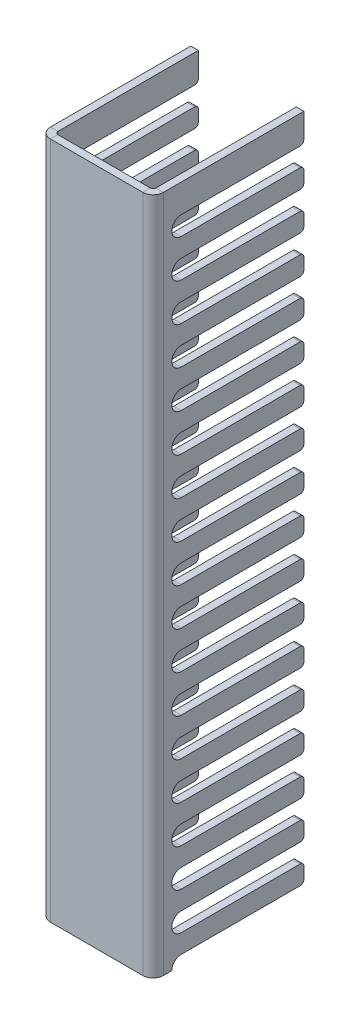
SolidWorks part; units mm, degrees
note: The reader was unsure of these and kept them because the rebuilt part matched: flange length of "边线-法兰1".
ref_plane "前视基准面" through (0, 0, 0) normal (0, 0, 1) x (1, 0, 0)
ref_plane "上视基准面" through (0, 0, 0) normal (0, 1, 0) x (1, 0, 0)
ref_plane "右视基准面" through (0, 0, 0) normal (1, 0, 0) x (0, 0, -1)
sketch "草图1" plane through (0, 0, 0) normal (0, 0, 1) x (1, 0, 0)
  line L1 (-18.0132, 35.6887) -> (11.9868, 35.6887)
  line L2 (-18.0132, 35.6887) -> (-18.0132, -144.3113)
  line L3 (-18.0132, -144.3113) -> (11.9868, -144.3113)
  line L4 (11.9868, 35.6887) -> (11.9868, -144.3113)
  dimension "D1" = 30
  dimension "D2" = 180
sheet metal parameters "钣金1" thickness 2 parameters "D1"=0.7366
base flange "基体-法兰1" sketch "草图1" thickness 2 reverse thickness direction no parameters "D1"=0.7366
edge flange "边线-法兰1" sketch "草图9" flange profiles "草图9", "草图10" flange angle 90 flange length 40 flange position material inside bend radius 0.7366 thickness 2 relief rectangular parameters "D6"=10, "D8"=1
sketch "草图9" plane through (11.9868, 0, -2) normal (1, 0, 0) x (0, -1, 0)
  line L2 (-35.6887, 0) -> (-35.6887, 38)
  line L3 (-35.6887, 38) -> (144.3113, 38)
  line L4 (144.3113, 38) -> (144.3113, 0)
  line L7 (144.3113, 0) -> (-35.6887, 0) construction
  line L8 (144.3113, 0) -> (-35.6887, 0)
sketch "草图10" plane through (-18.0132, 0, -2) normal (-1, 0, 0) x (0, 1, 0)
  line L0 (35.6887, 0) -> (-144.3113, 0) construction
  line L1 (35.6887, 0) -> (-144.3113, 0)
  line L2 (-144.3113, 0) -> (-144.3113, 38)
  line L3 (-144.3113, 38) -> (35.6887, 38)
  line L4 (35.6887, 38) -> (35.6887, 0)
bend "边线折弯1" bend radius 0.7366 bend angle 90 parameters "D5"=1
bend "边线折弯2" bend radius 0.7366 bend angle 90 parameters "D5"=2
sketch "草图11" plane through (-18.0132, 0, 0) normal (-1, 0, 0) x (0, 0, 1)
  line L0 (-7.45, 28.1887) -> (-39, 28.1887)
  line L3 (-39, 23.1887) -> (-7.45, 23.1887)
  line L4 (-40, 29.1887) -> (-40, 22.1887)
  arc A0 (-7.45, 23.1887) -> (-7.45, 28.1887) centre (-7.45, 25.6887) ccw
  arc A1 (-40, 29.1887) -> (-39, 28.1887) centre (-39, 29.1887) ccw
  arc A2 (-40, 22.1887) -> (-39, 23.1887) centre (-39, 22.1887) cw
  dimension "D1" = 10
  dimension "D4" = 1
  dimension "D5" = 1
extrude "切除-拉伸1" cut sketch "草图11" against normal blind 30 normal cut yes
pattern_linear "阵列(线性)1" count 19 spacing 10 along (0, -1, 0) of "切除-拉伸1"
flat pattern "平板型式1" [suppressed]
sketch "折弯-线1" plane through (0, 0, 0) normal (0, 0, 1) x (1, 0, 0)
  line L0 (-16.6406, 35.6887) -> (-16.6406, -144.3113) construction
  line L1 (10.6141, -144.3113) -> (10.6141, 35.6887) construction
  line L2 (-16.6406, 35.6887) -> (-16.6406, -144.3113) construction
  line L3 (10.6141, -144.3113) -> (10.6141, 35.6887) construction
sketch3d "边界框1" [suppressed]
  line L0 (49.2414, 35.6887, 0) -> (49.2414, -144.3113, 0) construction
  line L1 (-55.2679, 35.6887, 0) -> (-55.2679, -144.3113, 0) construction
  line L2 (49.2414, 35.6887, 0) -> (-55.2679, 35.6887, 0) construction
  line L3 (49.2414, -144.3113, 0) -> (-55.2679, -144.3113, 0) construction
bend of the flat pattern "展平-<边线折弯1>1"
bend of the flat pattern "展平-<边线折弯2>1"
